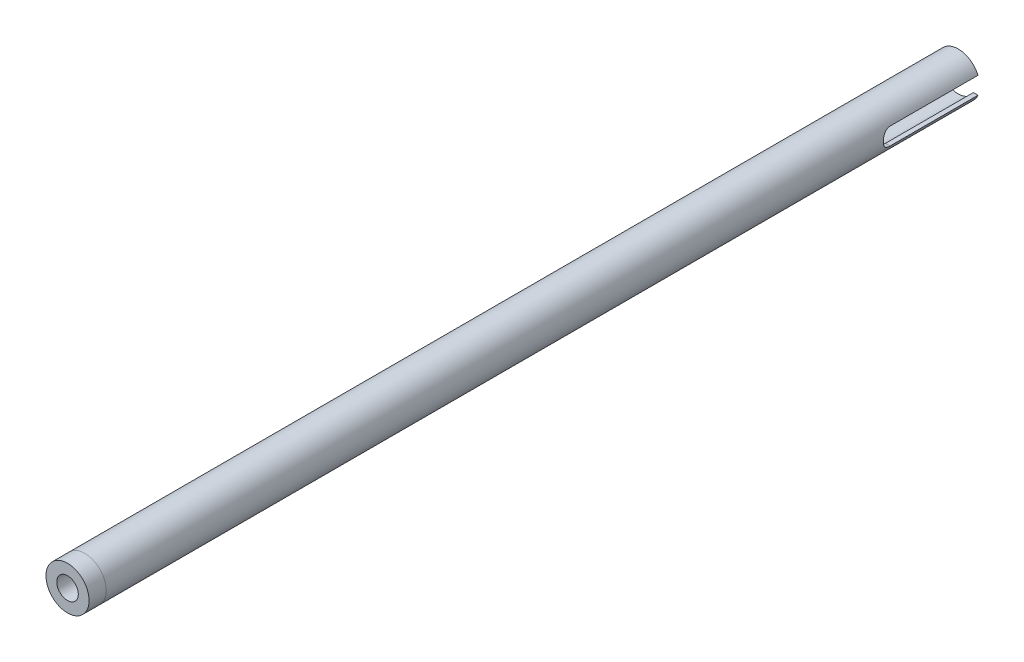
SolidWorks part; units mm, degrees
material "AISI 4130 Steel, annealed at 865C"
ref_plane "Front Plane" through (0, 0, 0) normal (0, 0, 1) x (1, 0, 0)
ref_plane "Top Plane" through (0, 0, 0) normal (0, 1, 0) x (1, 0, 0)
ref_plane "Right Plane" through (0, 0, 0) normal (1, 0, 0) x (0, 0, -1)
sketch "Axis" plane through (0, 0, 0) normal (0, 1, 0) x (1, 0, 0)
  line L0 (0, 0) -> (0, 328.0702) construction
  line L1 (0, 0) -> (0, -28.575) construction
  line L2 (0, 328.0702) -> (-7.9375, 328.0702) construction
  line L3 (0, 356.4735) -> (-26.4371, 261.8721) construction
  dimension "D1" = 28.575
  dimension "D2" = 7.9375
sketch "Sketch1" plane through (0, 0, 0) normal (0, 0, 1) x (1, 0, 0)
  line L0 (-7.9375, 0) -> (7.9375, 0) construction
  line L1 (-7.2748, 3.175) -> (7.2748, 3.175)
  line L2 (-7.2748, -3.175) -> (7.2748, -3.175)
  circle A0 centre (0, 0) radius 7.9375
  circle A1 centre (0, 0) radius 6.4135
  circle A2 centre (0, 0) radius 3.9688
  dimension "D1" = 15.875
  dimension "D3" = 7.9375
  dimension "D2" = 1.524
  dimension "D4" = 6.35
extrude "Threaded insert 1-1" add sketch "Sketch1" against normal blind 6.35 contours A2 L1 A1 | A1 L1 A0 | A2 L0 A1 L1 | A1 L0 A0 L1 | L0 A1 L2 A0 | L0 A2 L2 A1 | A2 L2 A1 | A1 L2 A0 | L0 A1 L2 A2 | L0 A0 L2 A1 | A0 L0 A1 L1 | A1 L0 A2 L1 region at (4.7887, 1.6543, 0) region at (4.7887, -1.6543, 0) region at (6.9234, 1.6163, 0) region at (6.9234, -1.6163, 0) region at (-4.7887, -1.6543, 0) region at (-4.7887, 1.6543, 0) region at (0, 4.6159, 0) region at (0, -4.6159, 0) region at (0, 6.5666, 0) region at (6.4237, -3.3281, 0) region at (-6.9234, -1.6163, 0) region at (-6.9234, 1.6163, 0)
extrude "Threaded insert 1-2" add sketch "Sketch1<3>" against normal blind 9.525 from surface contours A2 L1 A1 | A2 L0 A1 L1 | L0 A2 L2 A1 | A2 L2 A1 | L0 A1 L2 A2 | A1 L0 A2 L1 region at (4.7887, 1.6543, 0) region at (4.7887, -1.6543, 0) region at (-4.7887, -1.6543, 0) region at (-4.7887, 1.6543, 0) region at (0, 4.6159, 0) region at (0, -4.6159, 0) starting at face at (7.9375, 0, -6.35)
sketch "Sketch1<3>" plane through (0, 0, 0) normal (0, 0, 1) x (1, 0, 0) same geometry as "Sketch1"
extrude "A-arm tube" add sketch "Sketch1<4>" against normal up to vertex (328.0702 mm away) from surface separate body contours A1 L1 A0 | A1 L0 A0 L1 | L0 A1 L2 A0 | A1 L2 A0 | L0 A0 L2 A1 | A0 L0 A1 L1 region at (6.9234, 1.6163, 0) region at (6.9234, -1.6163, 0) region at (0, 6.5666, 0) region at (6.4237, -3.3281, 0) region at (-6.9234, -1.6163, 0) region at (-6.9234, 1.6163, 0) up to point (0, 0, -328.0702) starting at face at (6.4135, 0, -6.35)
sketch "Sketch1<4>" plane through (0, 0, 0) normal (0, 0, 1) x (1, 0, 0) same geometry as "Sketch1"
extrude "Apex slot" cut sketch "Sketch1<5>" along normal blind 35.56 from surface contours A0 L0 A1 L1 | L0 A0 L2 A1 | A1 L0 A0 L1 | L0 A1 L2 A0 region at (6.9234, 1.6163, 0) region at (6.9234, -1.6163, 0) region at (-6.9234, -1.6163, 0) region at (-6.9234, 1.6163, 0) starting at face at (6.4135, 0, -328.0702)
sketch "Sketch1<5>" plane through (0, 0, 0) normal (0, 0, 1) x (1, 0, 0) same geometry as "Sketch1"
fillet "Fillet1" radius 3.175 4 edges at (-6.4237, 3.175, -292.5102) (-6.4237, -3.175, -292.5102) (6.4237, -3.175, -292.5102) (6.4237, 3.175, -292.5102)
equation "\"tube diameter\"= 5 / 8"
equation "\"tube thickness\"= .06"
equation "\"apex thickness\"= .25"
equation "\"tube slot\"= 1.4"
equation "\"D1@Sketch1\"=\"tube diameter\""
equation "\"D2@Sketch1\"=\"tube thickness\""
equation "\"threaded insert hole\"= .3125"
equation "\"D3@Sketch1\"=\"threaded insert hole\""
equation "\"D4@Sketch1\"=\"apex thickness\""
equation "\"D1@Apex slot\" = \"tube slot\""
equation "\"D1@Fillet1\"=\"apex thickness\"/2"
